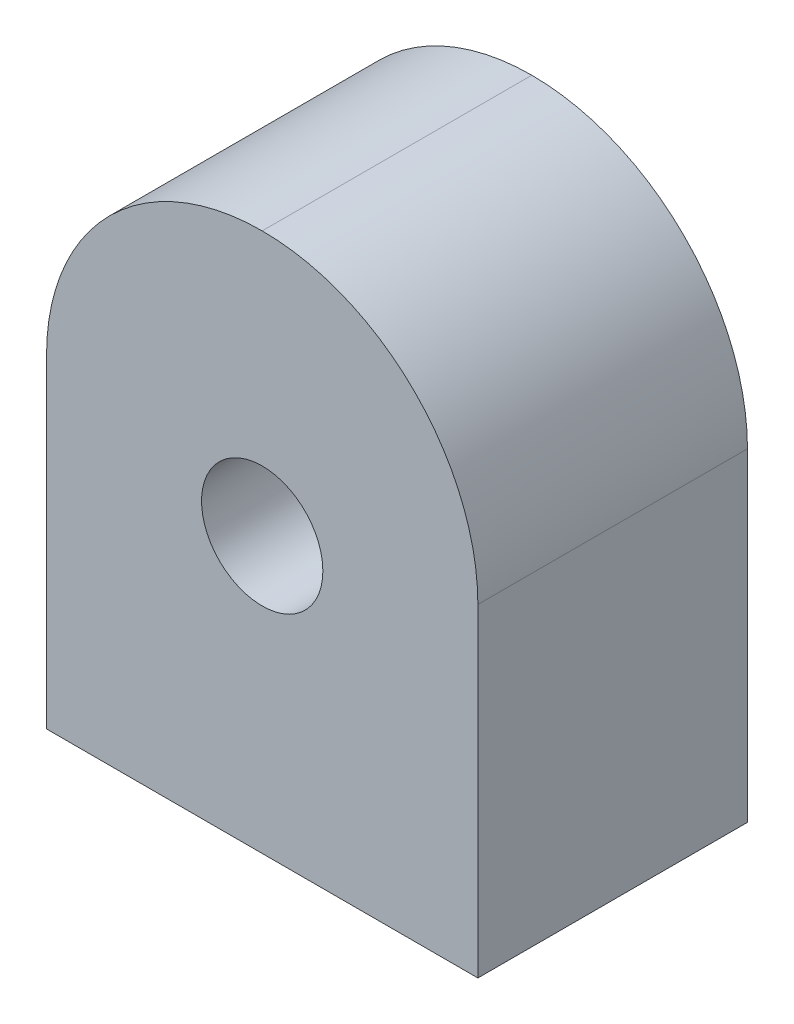
SolidWorks part; units mm, degrees
ref_plane "Front Plane" through (0, 0, 0) normal (0, 0, 1) x (1, 0, 0)
ref_plane "Top Plane" through (0, 0, 0) normal (0, 1, 0) x (1, 0, 0)
ref_plane "Right Plane" through (0, 0, 0) normal (1, 0, 0) x (0, 0, -1)
sketch "Sketch1" plane through (0, 0, 0) normal (0, 0, 1) x (1, 0, 0)
  line L1 (0, 0) -> (16, 0)
  line L2 (0, 0) -> (0, 20)
  line L3 (0, 20) -> (16, 20)
  line L4 (16, 0) -> (16, 20)
  dimension "D1" = 16
  dimension "D2" = 20
extrude "Boss-Extrude1" add sketch "Sketch1" along normal blind 10
sketch "Sketch2" plane through (0, 0, 10) normal (0, 0, 1) x (1, 0, 0)
  line L0 (8, 0) -> (8, 20) construction
  line L1 (0, 0) -> (16, 0) construction
  line L2 (16, 20) -> (0, 20) construction
  circle A0 centre (8, 10.2) radius 2.25
  dimension "D1" = 4.5
  dimension "D2" = 10.2
extrude "Cut-Extrude1" cut sketch "Sketch2" against normal through all
fillet "Fillet1" radius 8 2 edges at (16, 20, 5) (0, 20, 5)
